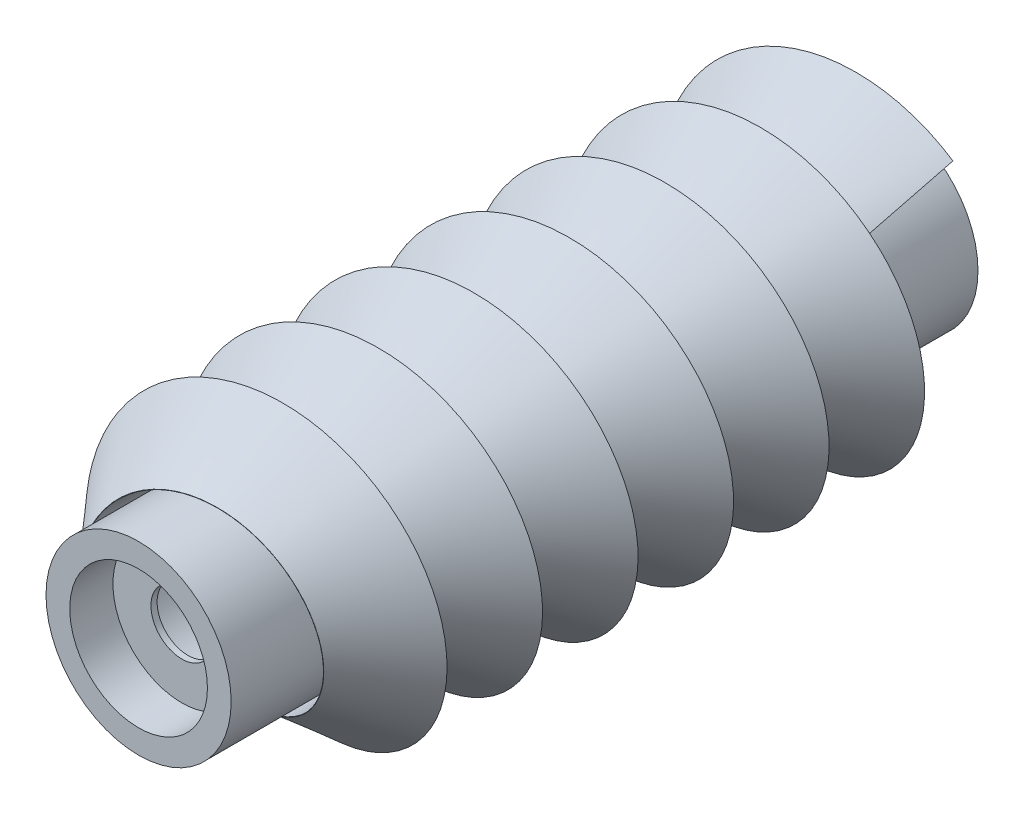
SolidWorks part; units mm, degrees
ref_plane "Спереди" through (0, 0, 0) normal (0, 0, 1) x (1, 0, 0)
ref_plane "Сверху" through (0, 0, 0) normal (0, 1, 0) x (1, 0, 0)
ref_plane "Справа" through (0, 0, 0) normal (1, 0, 0) x (0, 0, -1)
sketch "Эскиз1" plane through (0, 0, 0) normal (0, 0, 1) x (1, 0, 0)
  circle A0 centre (0, 0) radius 15
  circle A1 centre (0, 0) radius 11
  dimension "D1" = 22
  dimension "D2" = 30
extrude "Бобышка-Вытянуть1" add sketch "Эскиз1" along normal blind 63
sketch "Эскиз6" plane through (0, 0, 0) normal (0, 0, -1) x (-1, 0, 0)
  circle A0 centre (0, 0) radius 15 construction
  circle A1 centre (0, 0) radius 15
curve "Спираль1" pitch 15.4738 height 100.58 turns 6.5
ref_plane "Плоскость1" through (9.4398, 11.6572, 0) normal (-0.7669, 0.621, 0.162) x (0.119, -0.1105, 0.9867)
sketch "Эскиз7" plane through (9.4398, 11.6572, 0) normal (-0.7669, 0.621, 0.162) x (0.119, -0.1105, 0.9867)
  line L1 (0, 0) -> (16.3362, 0.9182)
  line L2 (0, 0) -> (5.6542, 10.3336)
  line L3 (5.6542, 10.3336) -> (16.3362, 0.9627)
  line L4 (16.3362, 0.9182) -> (16.3362, 0.9627)
  dimension "D1" = 16.3362
  dimension "D2" = 10
sweep "По траектории1" add profiles "Эскиз7" path "Спираль1"
sketch "Эскиз12" plane through (0, 0, 63) normal (0, 0, 1) x (1, 0, 0)
  circle A1 centre (0, 0) radius 15
  circle A2 centre (0, 0) radius 15
  dimension "D1" = 0
extrude "Бобышка-Вытянуть2" add sketch "Эскиз12" along normal blind 8
hole_wizard "Отверстие1" positions "Эскиз22" profile "Эскиз21" legacy
sketch "Эскиз22" plane through (0, 0, 71) normal (0, 0, 1) x (1, 0, 0)
  point P0 (0, 0)
sketch "Эскиз21" plane through (0, 0, 71) normal (1, 0, 0) x (0, -1, 0)
  line L0 (0, 0) -> (0, 7)
  line L1 (0, 7) -> (11.155, 7)
  line L2 (11.155, 7) -> (11.155, 0)
  line L3 (11.155, 0) -> (0, 0)
  line L4 (0, 110) -> (0, -10) construction
  dimension "Диаметр" = 22.31
  dimension "Глубина" = 7
sketch "Эскиз34" plane through (0, 0, 0) normal (0, 0, -1) x (-1, 0, 0)
  circle A1 centre (0, 0) radius 15
  circle A2 centre (0, 0) radius 15
  dimension "D1" = 0
extrude "Бобышка-Вытянуть6" add sketch "Эскиз34" along normal blind 60
move or copy body "Тело-Переместить/Копировать1" bodies to move or copy 104 copy no translate (0, 0, -50)
hole_wizard "Отверстие2" positions "Эскиз36" profile "Эскиз35" legacy
sketch "Эскиз36" plane through (0, 0, -60) normal (0, 0, -1) x (-1, 0, 0)
  point P0 (0, 0)
sketch "Эскиз35" plane through (0, 0, -60) normal (1, 0, 0) x (0, 1, 0)
  line L0 (0, 0) -> (0, 50)
  line L1 (0, 50) -> (14, 50)
  line L2 (14, 50) -> (14, 0)
  line L3 (14, 0) -> (0, 0)
  line L4 (0, 110) -> (0, -10) construction
  dimension "Диаметр" = 28
  dimension "Глубина" = 50
sketch "Эскиз43" plane through (0, 0, -10) normal (0, 0, -1) x (-1, 0, 0)
  line L2 (0.75, 2.2798) -> (0.75, -2.2798)
  arc A0 (0.75, 2.2798) -> (0.75, -2.2798) centre (0, 0) ccw
  dimension "D2" = 4.8
  dimension "D3" = 0.75
extrude "Вырез-Вытянуть2" cut sketch "Эскиз43" against normal blind 20 contours L2 A0
other "Переместить грань1" face at (-14, 0, -60) parameters "D1"=10
hole_wizard "Отверстие3" positions "Эскиз45" profile "Эскиз44" legacy
sketch "Эскиз45" plane through (0, 0, 64) normal (0, 0, 1) x (1, 0, 0)
  point P0 (0, 0)
sketch "Эскиз44" plane through (0, 0, 64) normal (1, 0, 0) x (0, -1, 0)
  line L0 (0, 0) -> (0, 20)
  line L1 (0, 20) -> (5, 20)
  line L2 (5, 20) -> (5, 0)
  line L3 (5, 0) -> (0, 0)
  line L4 (0, 110) -> (0, -10) construction
  dimension "Диаметр" = 10
  dimension "Глубина" = 20
ref_plane "Plane1" through (-0.75, -2.2798, 0) normal (-0.9499, 0.3125, 0) x (0, 0, 1)
